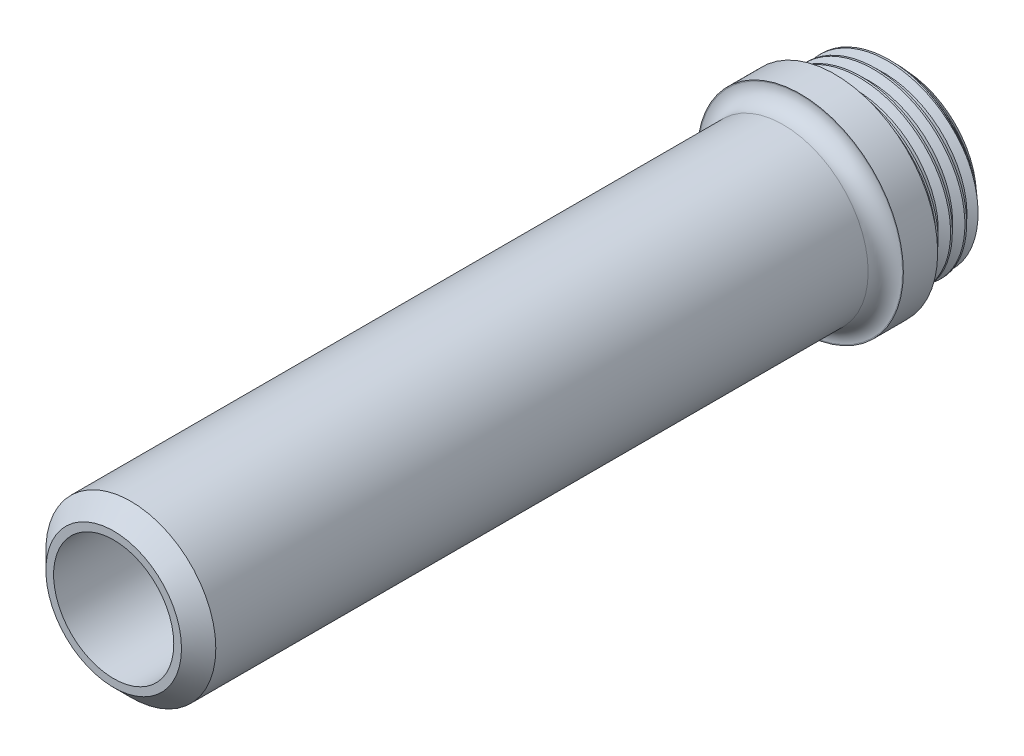
SolidWorks part; units mm, degrees
material "Plain Carbon Steel"
ref_plane "Front Plane" through (0, 0, 0) normal (0, 0, 1) x (1, 0, 0)
ref_plane "Top Plane" through (0, 0, 0) normal (0, 1, 0) x (1, 0, 0)
ref_plane "Right Plane" through (0, 0, 0) normal (1, 0, 0) x (0, 0, -1)
sketch "Sketch1" plane through (0, 0, 0) normal (0, 0, 1) x (1, 0, 0)
  circle A0 centre (0, 0) radius 7.62
  dimension "D1" = 15.24
extrude "Boss-Extrude1" add sketch "Sketch1" along normal blind 2.54
sketch "Sketch2" plane through (0, 0, 0) normal (0, 0, -1) x (-1, 0, 0)
  circle A0 centre (0, 0) radius 6.6675
  dimension "D1" = 13.335
extrude "Boss-Extrude2" add sketch "Sketch2" along normal blind 5.08
sketch "Sketch8" plane through (0, 0, 2.54) normal (0, 0, 1) x (1, 0, 0)
  circle A0 centre (0, 0) radius 6.2865
  dimension "D1" = 12.573
extrude "Boss-Extrude3" add sketch "Sketch8" along normal blind 50.8
thread "Thread1" pitch 1.0583 method cut profile "Thread Profile1" start angle 0, offset 0, length 5.461, pitch 1.0583, diameter 13.335
ref_plane "Plane1" through (6.6675, 0, -5.08) normal (0, -1, 0) x (1, 0, 0)
sketch "Thread Profile1" plane through (6.6675, 0, -5.08) normal (0, -1, 0) x (1, 0, 0)
  line L0 (0, 0) -> (0, 1.0583) construction
  line L11 (0, 0) -> (0, 0.926)
  line L12 (0, 0.926) -> (-0.5728, 0.5953)
  line L13 (-0.5728, 0.5953) -> (-0.5728, 0.3307)
  line L15 (-0.5728, 0.3307) -> (0, 0)
  line L17 (-0.5728, 0.463) -> (0, 0.463) construction
  point P2 (0, 0)
  dimension "Pitch" = 1.0583
  dimension "Profile_Angle" = 60
  dimension "Profile_Land" = 0.2646
  dimension "Profile_Height" = 0.5728
sketch "Sketch6" plane through (0, 0, 0) normal (0, 1, 0) x (1, 0, 0)
  line L0 (0, 0) -> (0, 5.08) construction
  line L1 (6.6675, 5.08) -> (-6.6675, 5.08) construction
  line L2 (4.699, 5.715) -> (7.239, 3.429)
  line L3 (7.239, 3.429) -> (7.239, 5.715)
  line L4 (7.239, 5.715) -> (4.699, 5.715)
  dimension "D1" = 4.699
  dimension "D2" = 2.54
  dimension "D3" = 2.286
  dimension "D4" = 0.635
revolve "Cut-Revolve1" cut sketch "Sketch6" angle 360 about L0
chamfer "Chamfer1" distance 1.27 angle 45 1 edges at (6.2865, 0, 53.34)
sketch "Sketch7" plane through (0, 0, 53.34) normal (0, 0, 1) x (1, 0, 0)
  circle A1 centre (0, 0) radius 4.445
  dimension "D1" = 8.89
extrude "Cut-Extrude1" cut sketch "Sketch7" against normal through all
fillet "Fillet1" radius 1.27 1 edges at (6.2865, 0, 2.54)
